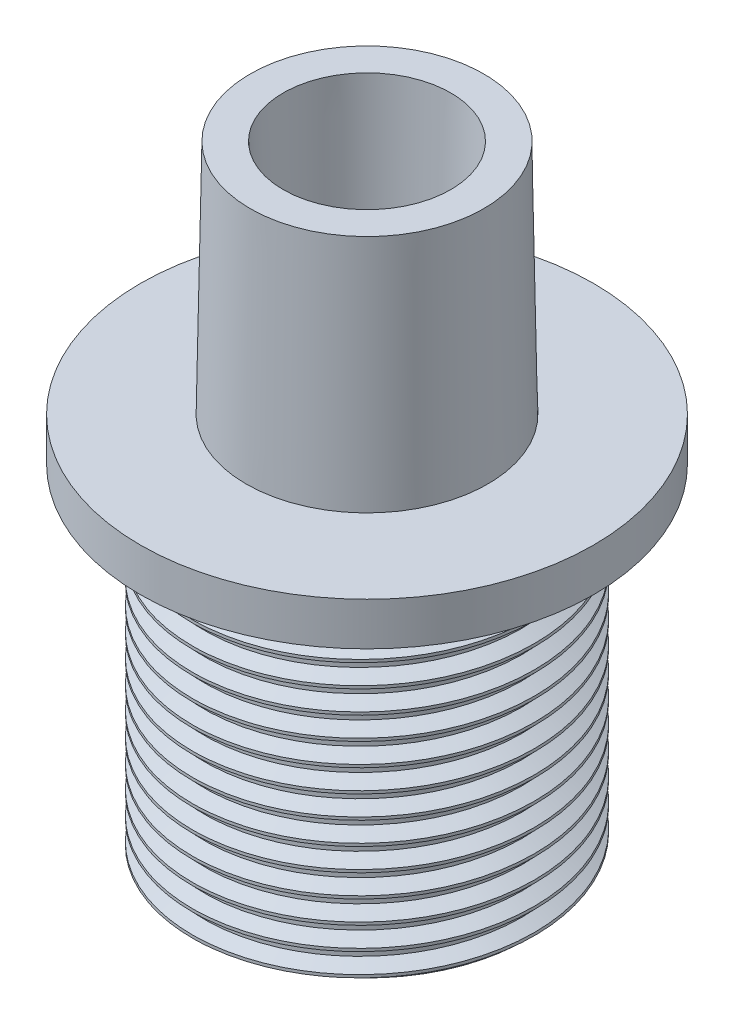
SolidWorks part; units mm, degrees
ref_plane "Front Plane" through (0, 0, 0) normal (0, 0, 1) x (1, 0, 0)
ref_plane "Top Plane" through (0, 0, 0) normal (0, 1, 0) x (1, 0, 0)
ref_plane "Right Plane" through (0, 0, 0) normal (1, 0, 0) x (0, 0, -1)
sketch "Sketch1" plane through (0, 0, 0) normal (0, 1, 0) x (1, 0, 0)
  circle A0 centre (0, 0) radius 15.9
  dimension "D1" = 31.8
extrude "Boss-Extrude1" add sketch "Sketch1" along normal blind 35
sketch "Sketch2" plane through (0, 0, 0) normal (0, -1, 0) x (1, 0, 0)
  circle A0 centre (0, 0) radius 11.65
  dimension "D1" = 23.3
extrude "Cut-Extrude1" cut sketch "Sketch2" against normal blind 25
sketch "Sketch5" plane through (0, 35, 0) normal (0, 1, 0) x (1, 0, 0)
  circle A0 centre (0, 0) radius 15.9
  circle A1 centre (0, 0) radius 21.0878
extrude "Boss-Extrude2" add sketch "Sketch5" against normal blind 4
thread "Thread1" pitch 2.1167 method cut profile "Thread Profile1" start angle 0, offset 5, length 34, pitch 2.1167, diameter 31.8
ref_plane "Plane1" through (15.9, -5, 0) normal (0, 0, 1) x (1, 0, 0)
sketch "Thread Profile1" plane through (15.9, -5, 0) normal (0, 0, 1) x (1, 0, 0)
  line L0 (0, 0) -> (0, 2.1167) construction
  line L11 (0, 0) -> (0, 1.8521)
  line L12 (0, 1.8521) -> (-1.1457, 1.1906)
  line L13 (-1.1457, 1.1906) -> (-1.1457, 0.6615)
  line L15 (-1.1457, 0.6615) -> (0, 0)
  line L17 (-1.1457, 0.926) -> (0, 0.926) construction
  point P2 (0, 0)
  dimension "Pitch" = 2.1167
  dimension "Profile_Angle" = 60
  dimension "Profile_Land" = 0.5292
  dimension "Profile_Height" = 1.1457
sketch "Sketch3" plane through (0, 35, 0) normal (0, 1, 0) x (1, 0, 0)
  circle A0 centre (0, 0) radius 11.25
  dimension "D1" = 22.5
extrude "Boss-Extrude3" add sketch "Sketch3" along normal blind 22 draft 1
sketch "Sketch7" plane through (0, 57, 0) normal (0, 1, 0) x (1, 0, 0)
  circle A0 centre (0, 0) radius 7.8
  dimension "D1" = 15.6
extrude "Cut-Extrude2" cut sketch "Sketch7" against normal up to next (32 mm away) draft 1.5
